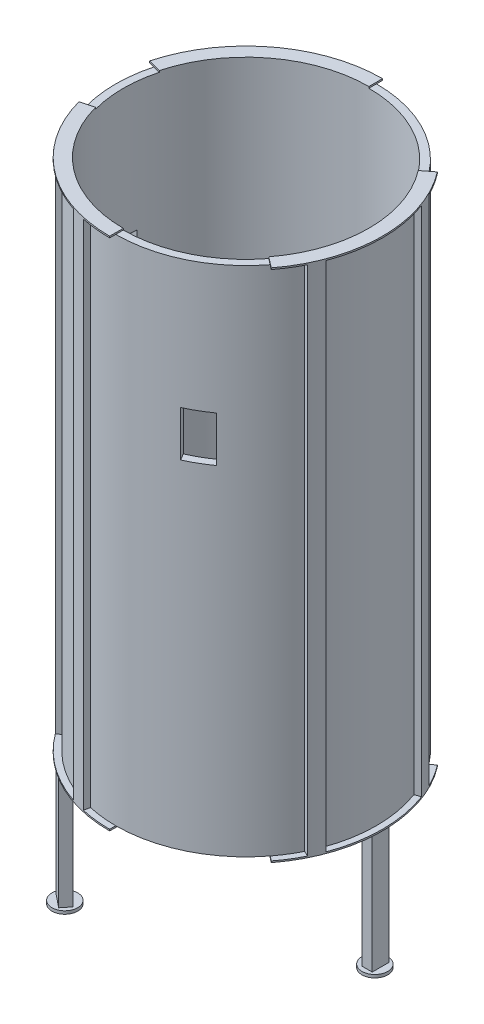
SolidWorks part; units mm, degrees
ref_plane "Ön Düzlem" through (0, 0, 0) normal (0, 0, 1) x (1, 0, 0)
ref_plane "Üst Düzlem" through (0, 0, 0) normal (0, 1, 0) x (1, 0, 0)
ref_plane "Sağ Düzlem" through (0, 0, 0) normal (1, 0, 0) x (0, 0, -1)
sketch "Çizim1" plane through (0, 0, 0) normal (0, 1, 0) x (1, 0, 0)
  circle A0 centre (0, 0) radius 858.5
  circle A1 centre (0, 0) radius 860
  dimension "D1" = 1717
  dimension "D2" = 1720
extrude "Yükseklik-Ekstrüzyon1" add sketch "Çizim1" along normal mid plane 3378
sketch "Çizim2" plane through (0, 0, 0) normal (0, 1, 0) x (1, 0, 0)
  circle A0 centre (0, 0) radius 858.5
  circle A1 centre (0, 0) radius 810
  dimension "D1" = 1717
  dimension "D2" = 1620
extrude "Yükseklik-Ekstrüzyon2" add sketch "Çizim2" along normal mid plane 3378 separate body
ref_plane "Düzlem1" through (0, 689, 0) normal (0, 1, 0) x (1, 0, 0)
sketch "Çizim3" plane through (0, 689, 0) normal (0, 1, 0) x (1, 0, 0)
  line L0 (0, 0) -> (-892.6994, 0) construction
  line L1 (0, 0) -> (429.25, -743.4828) construction
  line L2 (0, 0) -> (429.25, 743.4828) construction
  line L3 (370.8513, 816.6894) -> (521.8481, 729.5113)
  line L4 (-892.6994, -87.1781) -> (-802.0722, -87.1781)
  line L5 (-892.6994, -87.1781) -> (-892.6994, 87.1781)
  line L6 (-892.6994, 87.1781) -> (-802.0722, 87.1781)
  line L7 (-802.0722, -87.1781) -> (-802.0722, 87.1781)
  line L8 (-847.3858, 87.1781) -> (-847.3858, -87.1781) construction
  line L9 (-892.6994, 0) -> (-802.0722, 0) construction
  line L10 (370.8513, 816.6894) -> (325.5377, 738.2039)
  line L11 (325.5377, 738.2039) -> (476.5345, 651.0258)
  line L12 (521.8481, 729.5113) -> (476.5345, 651.0258)
  line L13 (521.8481, -729.5113) -> (370.8513, -816.6894)
  line L14 (370.8513, -816.6894) -> (325.5377, -738.2039)
  line L15 (476.5345, -651.0258) -> (325.5377, -738.2039)
  line L16 (521.8481, -729.5113) -> (476.5345, -651.0258)
  circle A0 centre (0, 0) radius 858.5 construction
  point P8 (-847.3858, 0)
  dimension "D1" = 120
  dimension "D2" = 120
  dimension "D3" = 2
  dimension "D4" = 2
extrude "Kes-Ekstrüzyon3" cut sketch "Çizim3" against normal mid plane 300
sketch "Çizim4" plane through (0, 1689, 0) normal (0, 1, 0) x (1, 0, 0)
  line L0 (0, -810) -> (0, -858.5)
  line L1 (-782.3999, -209.6434) -> (-829.2473, -222.1962)
  line L2 (0, 0) -> (-973.735, 0) construction
  line L3 (642.6162, -493.0968) -> (681.0938, -522.6217)
  line L4 (681.0938, 522.6217) -> (642.6162, 493.0968)
  line L5 (-782.3999, 209.6434) -> (-829.2473, 222.1962)
  line L6 (0, 810) -> (0, 858.5)
  arc A0 (681.0938, -522.6217) -> (681.0938, 522.6217) centre (0, 0) ccw
  circle A1 centre (0, 0) radius 858.5
  arc A2 (681.0938, -522.6217) -> (681.0938, 522.6217) centre (0, 0) ccw
  arc A3 (642.6162, -493.0968) -> (642.6162, 493.0968) centre (0, 0) ccw
  arc A4 (-782.3999, -209.6434) -> (0, -810) centre (0, 0) ccw
  arc A5 (-829.2473, -222.1962) -> (0, -858.5) centre (0, 0) ccw
  arc A6 (-829.2473, -222.1962) -> (0, -858.5) centre (0, 0) ccw
  circle A7 centre (0, 0) radius 858.5 construction
  arc A8 (-782.3999, 209.6434) -> (0, 810) centre (0, 0) cw
  arc A9 (-829.2473, 222.1962) -> (0, 858.5) centre (0, 0) cw
  point P1 (858.5, 0)
  point P2 (855.596, 70.5535)
  circle M7 centre (0, 0) radius 858.5
  circle M8 centre (0, 0) radius 810
  dimension "D3" = 1620
  dimension "D2" = 15
  dimension "D4" = 75
  dimension "D1" = 0
extrude "Yükseklik-Ekstrüzyon3" add sketch "Çizim4" along normal blind 10 separate body contours A9 L6 A8 L5
extrude "Yükseklik-Ekstrüzyon4" add sketch "Çizim4<3>" along normal blind 10 separate body contours L4 L3 M7 M8 | L1 L0 M8 M7 region at (-10.5293, 1689, 834.25) region at (777.12, 1689, 263.7967)
sketch "Çizim4<3>" plane through (0, 1689, 0) normal (0, 1, 0) x (1, 0, 0) same geometry as "Çizim4"
sketch "Çizim6" plane through (0, 1699, 0) normal (0, 1, 0) x (1, 0, 0)
  line L0 (-782.3999, -209.6434) -> (-869.3332, -232.9371)
  line L1 (0, -810) -> (0, -900)
  line L2 (642.6162, -493.0968) -> (714.018, -547.8853)
  line L3 (642.6162, 493.0968) -> (714.018, 547.8853)
  line L4 (-782.3999, 209.6434) -> (-869.3332, 232.9371)
  line L5 (0, 810) -> (0, 900)
  arc A0 (-869.3332, -232.9371) -> (0, -900) centre (0, 0) ccw
  arc A1 (-782.3999, -209.6434) -> (0, -810) centre (0, 0) ccw
  arc A3 (642.6162, -493.0968) -> (642.6162, 493.0968) centre (0, 0) ccw
  arc A4 (714.018, -547.8853) -> (714.018, 547.8853) centre (0, 0) ccw
  arc A5 (0, 810) -> (-782.3999, 209.6434) centre (0, 0) ccw
  arc A6 (0, 900) -> (-869.3332, 232.9371) centre (0, 0) ccw
  dimension "D1" = 900
extrude "Yükseklik-Ekstrüzyon6" add sketch "Çizim6" against normal blind 10 contours L0 A0 L1 A1 | L4 A6 L5 A5 | L2 A4 L3 A3
sketch "Çizim7" plane through (0, -1689, 0) normal (0, -1, 0) x (1, 0, 0)
  line L0 (-869.3332, -232.9371) -> (-782.3999, -209.6434)
  line L1 (-869.3332, 232.9371) -> (-782.3999, 209.6434)
  line L2 (0, 900) -> (0, 810)
  line L3 (0, -900) -> (0, -810)
  line L4 (714.018, -547.8853) -> (642.6162, -493.0968)
  line L5 (714.018, 547.8853) -> (642.6162, 493.0968)
  arc A0 (-782.3999, -209.6434) -> (0, -810) centre (0, 0) ccw
  arc A1 (-869.3332, -232.9371) -> (0, -900) centre (0, 0) ccw
  arc A2 (0, 810) -> (-782.3999, 209.6434) centre (0, 0) ccw
  arc A3 (0, 900) -> (-869.3332, 232.9371) centre (0, 0) ccw
  arc A4 (642.6162, -493.0968) -> (642.6162, 493.0968) centre (0, 0) ccw
  arc A5 (714.018, -547.8853) -> (714.018, 547.8853) centre (0, 0) ccw
extrude "Yükseklik-Ekstrüzyon7" add sketch "Çizim7" along normal blind 10 separate body
sketch "Çizim8" plane through (0, -1689, 0) normal (0, 1, 0) x (1, 0, 0)
  line L7 (-740.1333, 435) -> (-775.9114, 456.028)
  line L8 (-690.6089, 509.982) -> (-723.993, 534.6346)
  line L9 (-273.2, 813.8698) -> (-286.4065, 853.2123)
  line L10 (-186.6308, 837.9685) -> (-195.6526, 878.476)
  line L11 (0, 0) -> (-1420.4495, 0) construction
  line L12 (-273.2, -813.8698) -> (-286.4065, -853.2123)
  line L13 (-186.6308, -837.9685) -> (-195.6526, -878.476)
  line L14 (-740.1333, -435) -> (-775.9114, -456.028)
  line L15 (-690.6089, -509.982) -> (-723.993, -534.6346)
  line L16 (805.7667, -400.9239) -> (768.6119, -382.4369)
  line L17 (843.2606, -314.502) -> (804.3769, -300)
  line L18 (805.7667, 400.9239) -> (768.6119, 382.4369)
  line L19 (843.2606, 314.502) -> (804.3769, 300)
  arc A0 (805.7667, -400.9239) -> (843.2606, -314.502) centre (0, 0) ccw
  arc A1 (768.6119, -382.4369) -> (804.3769, -300) centre (0, 0) ccw
  arc A2 (-775.9114, -456.028) -> (-723.993, -534.6346) centre (0, 0) ccw
  arc A3 (-740.1333, -435) -> (-690.6089, -509.982) centre (0, 0) ccw
  arc A4 (-186.6308, 837.9685) -> (-273.2, 813.8698) centre (0, 0) ccw
  arc A5 (-195.6526, 878.476) -> (-286.4065, 853.2123) centre (0, 0) ccw
  arc A6 (804.3769, 300) -> (768.6119, 382.4369) centre (0, 0) ccw
  arc A7 (843.2606, 314.502) -> (805.7667, 400.9239) centre (0, 0) ccw
  arc A8 (-273.2, -813.8698) -> (-186.6308, -837.9685) centre (0, 0) ccw
  arc A9 (-286.4065, -853.2123) -> (-195.6526, -878.476) centre (0, 0) ccw
  arc A10 (-723.993, 534.6346) -> (-775.9114, 456.028) centre (0, 0) ccw
  arc A11 (-690.6089, 509.982) -> (-740.1333, 435) centre (0, 0) ccw
  dimension "D1" = 858.5
  dimension "D8" = 900
  dimension "D2" = 6
  dimension "D3" = 6
  dimension "D4" = 435
  dimension "D5" = 35
  dimension "D6" = 6
  dimension "D7" = 300
extrude "Yükseklik-Ekstrüzyon8" add sketch "Çizim8" along normal up to next
sketch "Çizim9" plane through (0, -1699, 0) normal (0, -1, 0) x (1, 0, 0)
  line L0 (-514.1799, -721.8631) -> (-600, -653.0524)
  line L5 (-600, -653.0524) -> (-557.4625, -600)
  line L6 (-557.4625, -600) -> (-471.6424, -668.8107)
  line L7 (-471.6424, -668.8107) -> (-514.1799, -721.8631)
  line L8 (0, 0) -> (-1353.9927, 0) construction
  line L9 (0, 0) -> (540.7638, 0) construction
  line L10 (-557.4625, 600) -> (-471.6424, 668.8107)
  line L11 (-600, 653.0524) -> (-557.4625, 600)
  line L12 (-514.1799, 721.8631) -> (-600, 653.0524)
  line L13 (-471.6424, 668.8107) -> (-514.1799, 721.8631)
  line L15 (819, -55) -> (887, -55)
  line L16 (819, -55) -> (819, 55)
  line L17 (819, 55) -> (887, 55)
  line L18 (887, -55) -> (887, 55)
  line L19 (853, 55) -> (853, -55) construction
  line L20 (819, 0) -> (887, 0) construction
  point P4 (-582.0625, -626.2759)
  point P13 (853, 0)
  dimension "D1" = 110
  dimension "D2" = 68
  dimension "D3" = 68
  dimension "D4" = 110
  dimension "D5" = 600
  dimension "D6" = 668.8107
  dimension "D7" = 600
  dimension "D8" = 853
extrude "Yükseklik-Ekstrüzyon9" add sketch "Çizim9" along normal blind 805
sketch "Çizim10" plane through (0, -2504, 0) normal (0, -1, 0) x (1, 0, 0)
  circle A0 centre (849.4151, 0) radius 85
  circle A1 centre (-537.0054, -660.3653) radius 85
  circle A2 centre (-537.0054, 658.6401) radius 85
  point P6 (-537.0054, 658.6401)
  point P7 (-537.0054, -660.3653)
  point P8 (849.4151, 0)
  dimension "D1" = 170
  dimension "D2" = 170
  dimension "D3" = 170
extrude "Yükseklik-Ekstrüzyon10" add sketch "Çizim10" against normal blind 20
